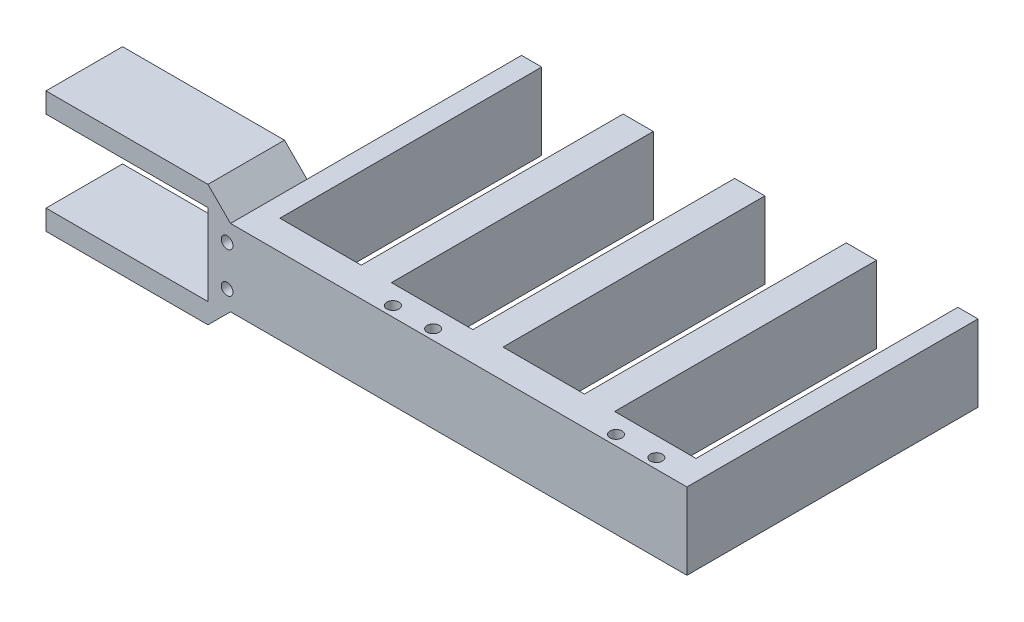
SolidWorks part; units mm, degrees
ref_plane "Front Plane" through (0, 0, 0) normal (1, 0, 0) x (0, 1, 0)
ref_plane "Top Plane" through (0, 0, 0) normal (0, 0, 1) x (0, 1, 0)
ref_plane "Right Plane" through (0, 0, 0) normal (0, 1, 0) x (-1, 0, 0)
sketch "Sketch2" plane through (0, 0, 0) normal (0, 1, 0) x (-1, 0, 0)
  line L33 (-23.95, 28.875) -> (-3.75, 28.875)
  line L38 (-51.65, -36.125) -> (-31.45, -36.125) construction
  line L39 (-51.65, -36.125) -> (-51.65, 28.875) construction
  line L40 (-51.65, 28.875) -> (-31.45, 28.875) construction
  line L41 (-31.45, -36.125) -> (-31.45, 28.875) construction
  line L42 (-51.65, -36.125) -> (-31.45, 28.875) construction
  line L43 (-51.65, 28.875) -> (-31.45, -36.125) construction
  line L44 (-23.95, -36.125) -> (-3.75, -36.125) construction
  line L45 (-23.95, -36.125) -> (-23.95, 28.875) construction
  line L46 (-23.95, 28.875) -> (-3.75, 28.875) construction
  line L47 (-3.75, -36.125) -> (-3.75, 28.875) construction
  line L48 (-23.95, -36.125) -> (-3.75, 28.875) construction
  line L49 (-23.95, 28.875) -> (-3.75, -36.125) construction
  line L50 (3.75, -36.125) -> (23.95, -36.125) construction
  line L51 (3.75, -36.125) -> (3.75, 28.875) construction
  line L52 (3.75, 28.875) -> (23.95, 28.875) construction
  line L53 (23.95, -36.125) -> (23.95, 28.875) construction
  line L54 (3.75, -36.125) -> (23.95, 28.875) construction
  line L55 (3.75, 28.875) -> (23.95, -36.125) construction
  line L56 (31.45, -36.125) -> (51.65, -36.125) construction
  line L57 (31.45, -36.125) -> (31.45, 28.875) construction
  line L58 (31.45, 28.875) -> (51.65, 28.875) construction
  line L59 (51.65, -36.125) -> (51.65, 28.875) construction
  line L60 (31.45, -36.125) -> (51.65, 28.875) construction
  line L61 (31.45, 28.875) -> (51.65, -36.125) construction
  line L62 (-56.65, -36.125) -> (-51.65, -36.125)
  line L65 (-51.65, -36.125) -> (-51.65, 28.875)
  line L66 (-56.65, 36.125) -> (-56.65, -36.125)
  line L67 (56.65, 36.125) -> (56.65, -36.125)
  line L69 (-31.45, 28.875) -> (-31.45, -36.125)
  line L70 (-31.45, -36.125) -> (-23.95, -36.125)
  line L71 (-23.95, 28.875) -> (-23.95, -36.125)
  line L72 (-56.65, 36.125) -> (56.65, -36.125) construction
  line L74 (-3.75, -36.125) -> (3.75, -36.125)
  line L75 (-3.75, -36.125) -> (-3.75, 28.875)
  line L77 (3.75, -36.125) -> (3.75, 28.875)
  line L81 (23.95, 28.875) -> (23.95, -36.125)
  line L82 (23.95, -36.125) -> (31.45, -36.125)
  line L83 (31.45, 28.875) -> (31.45, -36.125)
  line L86 (51.65, -36.125) -> (56.65, -36.125)
  line L87 (51.65, -36.125) -> (51.65, 28.875)
  line L92 (-51.65, 28.875) -> (-31.45, 28.875)
  line L94 (-56.65, 36.125) -> (56.65, 36.125)
  line L96 (3.75, 28.875) -> (23.95, 28.875)
  line L97 (31.45, 28.875) -> (51.65, 28.875)
  point P4 (-41.55, -3.625)
  point P7 (60.4, 38.0793)
  point P9 (-13.85, -3.625)
  point P14 (13.85, -3.625)
  point P19 (41.55, -3.625)
  dimension "D3" = 7.5
  dimension "D4" = 5
  dimension "D1" = 20.2
  dimension "D2" = 65
  dimension "D5" = 7.25
extrude "Boss-Extrude1" add sketch "Sketch2" along normal blind 9.5 and the other way blind 9.5
sketch "Sketch3" plane through (0, 0, 36.125) normal (0, 0, 1) x (1, 0, 0)
  line L0 (-56.65, 9.5) -> (-62.25, 15.1)
  line L1 (-56.65, -9.5) -> (-56.65, 9.5) construction
  line L2 (-56.65, 9.5) -> (56.65, 9.5) construction
  line L3 (-62.25, 15.1) -> (-102.45, 15.1)
  line L4 (-102.45, 15.1) -> (-102.45, 10.1)
  line L5 (-102.45, 10.1) -> (-62.25, 10.1)
  line L6 (-62.25, 10.1) -> (-62.25, -10.1)
  line L7 (-62.25, -10.1) -> (-102.45, -10.1)
  line L8 (-102.45, -10.1) -> (-102.45, -15.1)
  line L9 (-102.45, -15.1) -> (-62.25, -15.1)
  line L10 (-62.25, -15.1) -> (-56.65, -9.5)
  line L11 (-56.65, 9.5) -> (-56.65, -9.5)
  dimension "D1" = 20.2
  dimension "D2" = 40.2
  dimension "D3" = 135
  dimension "D4" = 5
extrude "Boss-Extrude2" add sketch "Sketch3" against normal blind 19
sketch "Sketch4" plane through (0, 0, 36.125) normal (0, 0, 1) x (1, 0, 0)
  line L0 (-62.25, 10.1) -> (-62.25, -10.1) construction
  line L1 (-57.5, 5) -> (-57.5, -5) construction
  circle A0 centre (-57.5, 5) radius 1.45
  circle A1 centre (-57.5, -5) radius 1.45
  point P4 (-62.25, 0)
  point P5 (-57.5, 0)
  point P6 (0, 0)
  dimension "D1" = 10
  dimension "D2" = 2.9
  dimension "D3" = 4.75
extrude "Cut-Extrude1" cut sketch "Sketch4" against normal blind 10
sketch "Sketch5" plane through (0, 9.5, 0) normal (0, 1, 0) x (-1, 0, 0)
  line L0 (-46.55, 33.625) -> (-36.55, 33.625) construction
  line L1 (8.85, 33.625) -> (18.85, 33.625) construction
  line L2 (-51.65, 28.875) -> (-31.45, 28.875) construction
  line L3 (3.75, 28.875) -> (23.95, 28.875) construction
  circle A0 centre (-46.55, 33.625) radius 1.5
  circle A1 centre (-36.55, 33.625) radius 1.5
  circle A2 centre (8.85, 33.625) radius 1.5
  circle A3 centre (18.85, 33.625) radius 1.5
  point P8 (-41.55, 28.875)
  point P9 (13.85, 28.875)
  point P12 (0, 0)
  point P15 (13.85, 33.625)
  point P16 (-41.55, 33.625)
  dimension "D1" = 4.75
  dimension "D2" = 3
  dimension "D3" = 10
extrude "Cut-Extrude2" cut sketch "Sketch5" against normal blind 10
sketch "Sketch6" plane through (0, -9.5, 0) normal (0, -1, 0) x (1, 0, 0)
  line L0 (-46.55, 33.625) -> (-36.55, 33.625) construction
  line L1 (9.2546, 33.625) -> (19.2546, 33.625) construction
  line L2 (-31.45, 28.875) -> (-51.65, 28.875) construction
  line L3 (23.95, 28.875) -> (3.75, 28.875) construction
  circle A0 centre (-46.55, 33.625) radius 1.45
  circle A1 centre (-36.55, 33.625) radius 1.45
  circle A2 centre (9.2546, 33.625) radius 1.45
  circle A3 centre (19.2546, 33.625) radius 1.45
  point P8 (-41.55, 33.625)
  point P9 (14.2546, 33.625)
  point P10 (-41.55, 28.875)
  point P11 (14.2546, 28.875)
  point P12 (-46.87, 32.204)
  dimension "D1" = 2.9
  dimension "D2" = 10
  dimension "D3" = 4.75
extrude "Cut-Extrude3" cut sketch "Sketch6" against normal blind 10
sketch "Sketch7" plane through (0, 0, -36.125) normal (0, 0, -1) x (1, 0, 0)
  line L0 (-23.95, 9.5) -> (-31.45, 9.5) construction
  line L1 (31.45, 9.5) -> (23.95, 9.5) construction
  circle A0 centre (-27.7, 0) radius 1.45
  circle A1 centre (27.7, 0) radius 1.45
  point P4 (-27.7, 9.5)
  point P6 (27.7, 9.5)
  point P9 (0, 0)
  point P12 (0, 0)
  dimension "D1" = 2.9
extrude "Cut-Extrude4" cut sketch "Sketch7" against normal blind 10
